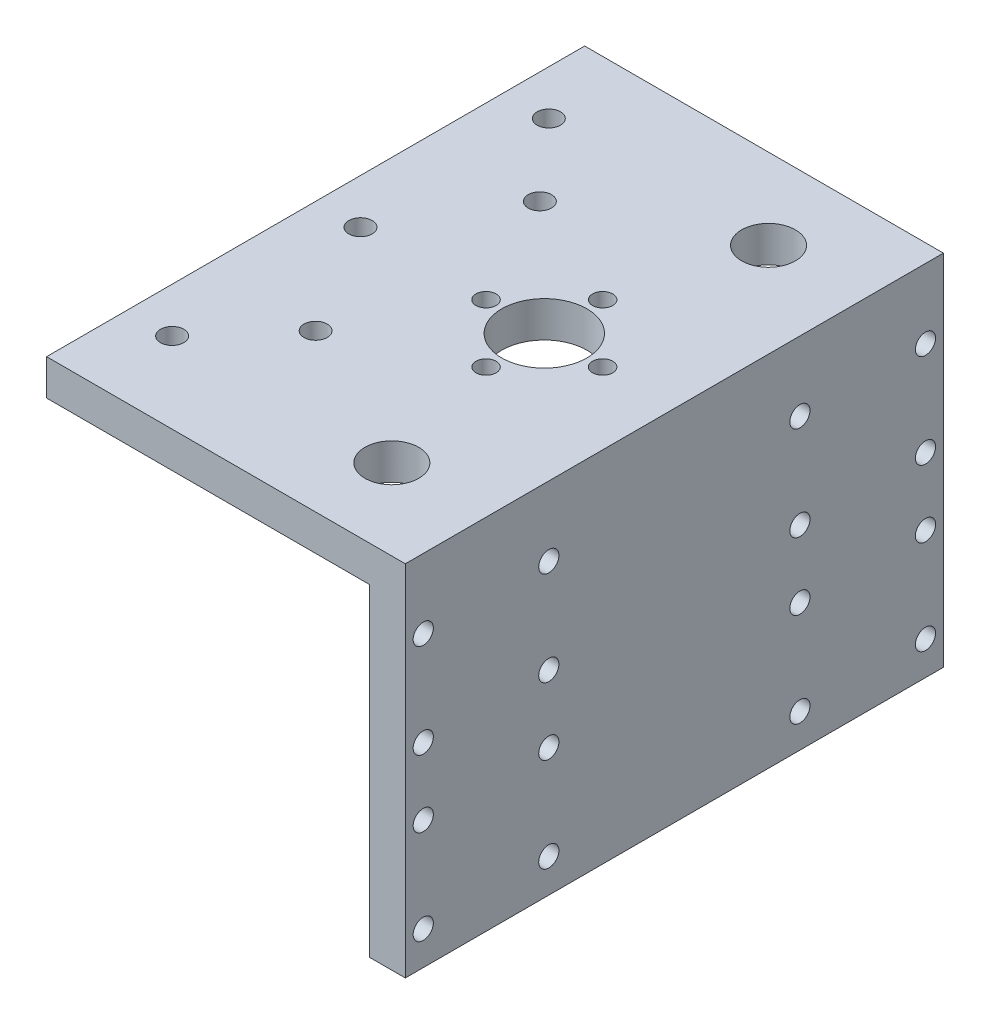
SolidWorks part; units mm, degrees
material "Lega 1060"
ref_plane "Piano frontale" through (0, 0, 0) normal (0, 0, 1) x (1, 0, 0)
ref_plane "Piano superiore" through (0, 0, 0) normal (0, 1, 0) x (1, 0, 0)
ref_plane "Piano destro" through (0, 0, 0) normal (1, 0, 0) x (0, 0, -1)
sketch "Schizzo1" plane through (0, 0, 0) normal (0, 0, 1) x (1, 0, 0)
  line L0 (0, 0) -> (-80, 0)
  line L1 (-80, 0) -> (-80, -8)
  line L2 (-80, -8) -> (-8, -8)
  line L3 (-8, -8) -> (-8, -80)
  line L4 (-8, -80) -> (0, -80)
  line L5 (0, -80) -> (0, 0)
  dimension "D1" = 80
  dimension "D2" = 80
  dimension "D3" = 8
  dimension "D4" = 8
extrude "Estrusione-Estrusione1" add sketch "Schizzo1" along normal blind 120
sketch "Schizzo12" plane through (0, 0, 0) normal (1, 0, 0) x (0, 0, -1)
  line L0 (-60, 0) -> (-60, -80) construction
  line L1 (-120, 0) -> (0, 0) construction
  line L2 (-120, -80) -> (0, -80) construction
  line L3 (-18, -24) -> (-18, 0) construction
  line L4 (-102, -24) -> (-102, 0) construction
  line L5 (-102, -62) -> (-18, -62) construction
  line L8 (-18, -26) -> (-102, -26) construction
  circle A0 centre (-116, -15.5) radius 2.25
  circle A1 centre (-88, -15.5) radius 2.25
  circle A2 centre (-88, -36.5) radius 2.25
  circle A3 centre (-116, -36.5) radius 2.25
  circle A4 centre (-32, -36.5) radius 2.25
  circle A5 centre (-4, -36.5) radius 2.25
  circle A6 centre (-32, -15.5) radius 2.25
  circle A7 centre (-4, -15.5) radius 2.25
  circle A8 centre (-116, -51.5) radius 2.25
  circle A9 centre (-88, -51.5) radius 2.25
  circle A10 centre (-88, -72.5) radius 2.25
  circle A11 centre (-116, -72.5) radius 2.25
  circle A12 centre (-4, -72.5) radius 2.25
  circle A13 centre (-32, -72.5) radius 2.25
  circle A14 centre (-32, -51.5) radius 2.25
  circle A15 centre (-4, -51.5) radius 2.25
  dimension "D1" = 4.5
  dimension "D5" = 4.5
  dimension "D2" = 14
  dimension "D3" = 10.5
  dimension "D4" = 36
  dimension "D6" = 14
  dimension "D7" = 10.5
  dimension "D8" = 26
  dimension "D9" = 18
sketch "Schizzo6" plane through (0, 0, 0) normal (0, 1, 0) x (1, 0, 0)
  line L0 (-21, -0.5808) -> (-21, -110.5835) construction
  line L2 (0, 0) -> (-80, 0) construction
  line L3 (-32.5218, -60) -> (-8.0464, -60) construction
  line L6 (0, -120) -> (-80, -120) construction
  circle A0 centre (-21, -18) radius 6
  circle A1 centre (-21, -102) radius 6
  dimension "D2" = 12
  dimension "D1" = 13
  dimension "D3" = 18
extrude "Taglio-Estrusione2" cut sketch "Schizzo6" against normal up to next
sketch "Schizzo7" plane through (0, 0, 0) normal (0, 1, 0) x (1, 0, 0)
  line L0 (-53.636, -60) -> (3.6289, -60) construction
  line L1 (0, -120) -> (-80, -120) construction
  line L2 (0, 0) -> (-80, 0) construction
  line L3 (-21, -18) -> (-21, -102) construction
  circle A0 centre (-29, -60) radius 9.5
  dimension "D1" = 19
  dimension "D2" = 8
extrude "Taglio-Estrusione3" cut sketch "Schizzo7" against normal up to next
hole_wizard "Foro per Vite M4-2" positions "Schizzo9" profile "Schizzo8" hole size "M4" standard "ISO" end condition through all
sketch "Schizzo9" plane through (0, 0, 0) normal (0, 1, 0) x (1, 0, 0)
  line L0 (-18.4657, -60) -> (-16, -60) construction
  line L2 (-29, -57.7684) -> (-29, -66.5063) construction
  circle A2 centre (-29, -60) radius 9.5 construction
  point P0 (-29, -47)
  point P2 (-42, -60)
  point P4 (-29, -73)
  point P8 (-16, -60)
  point P20 (-29, -60)
  dimension "D1" = 26
  dimension "D2" = 13
  dimension "D3" = 13
sketch "Schizzo8" plane through (-29, 0, 47) normal (1, 0, 0) x (0, 0, 1)
  line L0 (0, 0) -> (0, 80)
  line L1 (0, 80) -> (2.25, 80)
  line L2 (2.25, 80) -> (2.25, 0)
  line L5 (2.25, 0) -> (0, 0)
  line L11 (0, -6.35) -> (0, 107.95) construction
  dimension "Thru Hole Dia." = 4.5
  dimension "Thru Hole Depth" = 80
extrude "Taglio-Estrusione4" cut sketch "Schizzo12" against normal blind 10
sketch "Schizzo14" plane through (0, 0, 0) normal (0, 1, 0) x (1, 0, 0)
  line L0 (-70, 0) -> (-70, -120) construction
  line L1 (0, 0) -> (-80, 0) construction
  line L2 (0, -120) -> (-80, -120) construction
  line L3 (-80, -120) -> (-80, 0) construction
  line L4 (-55, 0) -> (-55, -120) construction
  line L5 (-21, -102) -> (-80, -102) construction
  line L6 (-80, -60) -> (0, -60) construction
  line L7 (0, -120) -> (0, 0) construction
  line L8 (-21, -18) -> (-80, -18) construction
  circle A0 centre (-70, -18) radius 2.6
  circle A1 centre (-70, -60) radius 2.6
  circle A2 centre (-70, -102) radius 2.6
  circle A3 centre (-55, -35) radius 2.6
  circle A4 centre (-55, -85) radius 2.6
  dimension "D3" = 5.2
  dimension "D4" = 5.2
  dimension "D5" = 5.2
  dimension "D6" = 5.2
  dimension "D7" = 5.2
  dimension "D1" = 10
  dimension "D2" = 25
  dimension "D8" = 35
  dimension "D9" = 35
extrude "Taglio-Estrusione5" cut sketch "Schizzo14" against normal blind 10
